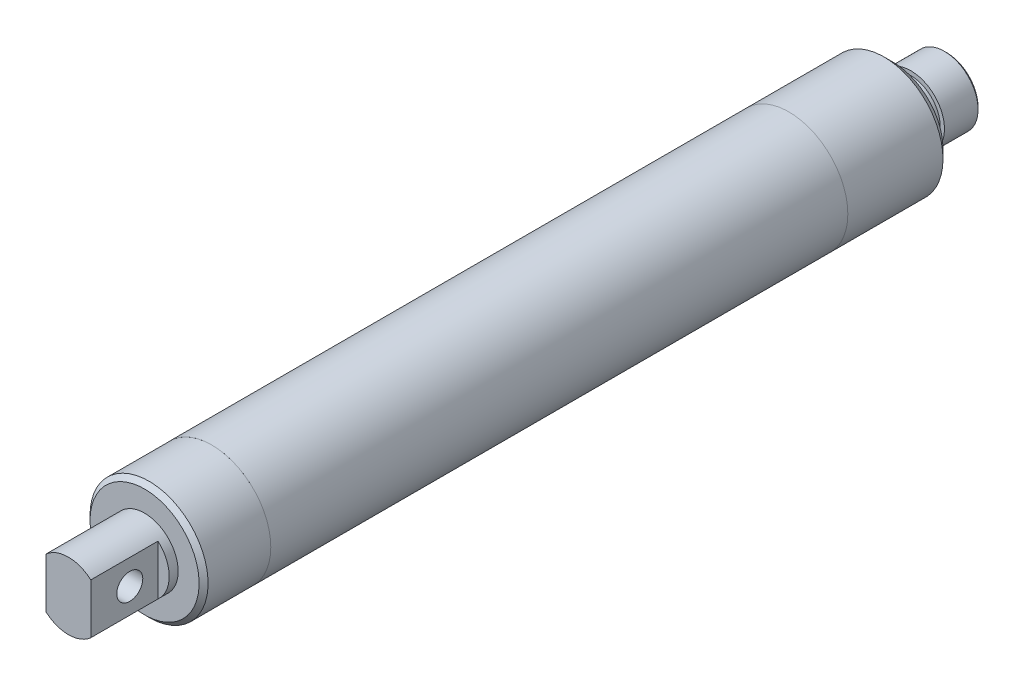
SolidWorks part; units mm, degrees
note: '?' marks a value the reader was unsure of.
ref_plane "Front" through (0, 0, 0) normal (0, 0, 1) x (1, 0, 0)
ref_plane "Top" through (0, 0, 0) normal (0, 1, 0) x (1, 0, 0)
ref_plane "Right" through (0, 0, 0) normal (1, 0, 0) x (0, 0, -1)
sketch "Sketch1" plane through (0, 0, 0) normal (0, 0, 1) x (1, 0, 0)
  circle A0 centre (0, 0) radius 16.7322
  circle A1 centre (0, 0) radius 15.4039
  dimension "D1" = 33.4645
extrude "Cyclendar" add sketch "Sketch1" along normal blind 163.576
ref_plane "Plane1" through (0, 0, 81.788) normal (0, 0, 1) x (1, 0, 0)
sketch "Sketch2" plane through (0, 0, 0) normal (0, 0, 1) x (1, 0, 0)
  circle A0 centre (0, 0) radius 16.7322
  circle A1 centre (0, 0) radius 5.588
  dimension "D1" = 11.176
extrude "Nose" add sketch "Sketch2" against normal blind 29.5148 separate body
chamfer "Nose_Chamfer" distance 2.54 angle 45 1 edges at (16.7322, 0, -29.5148)
sketch "Sketch3" plane through (0, 0, 0) normal (1, 0, 0) x (0, 0, -1)
  line L0 (0, 0) -> (11.049, 0) construction
  circle A0 centre (11.049, 0) radius 5.08
  dimension "D2" = 10.16
  dimension "D1" = 11.049
extrude "Cut-Extrude1" cut sketch "Sketch3" against normal up to next
sketch "Sketch4" plane through (0, 0, 0) normal (0, 1, 0) x (1, 0, 0)
  line L1 (-8.89, 44.7548) -> (-9.525, 44.1198)
  line L3 (-5.588, 44.7548) -> (-8.89, 44.7548)
  line L4 (-9.525, 44.1198) -> (-9.525, 34.5948)
  line L6 (-8.3185, 34.5948) -> (-8.3185, 31.4198)
  line L7 (-8.3185, 31.4198) -> (-9.525, 31.4198)
  line L8 (-9.525, 31.4198) -> (-9.525, 29.5148)
  line L9 (-9.525, 29.5148) -> (-5.588, 29.5148)
  line L10 (-9.525, 34.5948) -> (-8.3185, 34.5948)
  line L11 (-5.588, 29.5148) -> (-5.588, 44.7548)
  point P6 (-9.525, 44.7548)
ref_axis "Axis1" through (0, 0, -26.9748) along (0, 0, 1)?
revolve "Revolve1" add sketch "Sketch4" angle 360 about axis through (0, 0, -26.9748) along (0, 0, 1)
sketch "Sketch6" plane through (0, 0, 163.576) normal (0, 0, 1) x (1, 0, 0)
  circle A0 centre (0, 0) radius 16.7322 construction
  circle A1 centre (0, 0) radius 16.7322
extrude "Tail" add sketch "Sketch6" along normal blind 19.05 separate body
chamfer "Tail_Chamfer" distance 1.27 angle 45 1 edges at (16.7322, 0, 182.626)
sketch "Sketch7" plane through (0, 0, 182.626) normal (0, 0, 1) x (1, 0, 0)
  circle A0 centre (0, 0) radius 9.525
  dimension "D1" = 19.05
extrude "Tail_Mount" add sketch "Sketch7" along normal blind 2.54
sketch "Sketch8" plane through (0, 0, 185.166) normal (0, 0, 1) x (1, 0, 0)
  circle A0 centre (0, 0) radius 9.525 construction
  circle A1 centre (0, 0) radius 9.525
extrude "Boss-Extrude5" add sketch "Sketch8" along normal blind 19.05
sketch "Sketch9" plane through (0, 0, 0) normal (1, 0, 0) x (0, 0, -1)
  line L0 (-163.576, 16.7322) -> (-163.576, -16.7322) construction
  line L1 (-163.576, 16.7322) -> (-163.576, -16.7322) construction
  line L2 (-163.576, 0) -> (-174.752, 0) construction
  circle A0 centre (-174.752, 0) radius 5.08
  dimension "D2" = 10.16
  dimension "D1" = 11.176
extrude "Cut-Extrude2" cut sketch "Sketch9" against normal up to next
sketch "Sketch10" plane through (0, 0, 204.216) normal (0, 0, 1) x (1, 0, 0)
  line L0 (0, -9.525) -> (0, 9.525) construction
  line L1 (6.35, -9.525) -> (6.35, 9.525)
  line L2 (-6.35, -9.525) -> (-6.35, 9.525)
  line L3 (-6.35, -9.525) -> (-12.7995, -9.525)
  line L4 (-12.7995, -9.525) -> (-12.7995, 9.525)
  line L5 (-12.7995, 9.525) -> (-6.35, 9.525)
  line L6 (6.35, -9.525) -> (14.8147, -9.525)
  line L7 (14.8147, -9.525) -> (14.8147, 9.525)
  line L8 (14.8147, 9.525) -> (6.35, 9.525)
  circle A2 centre (0, 0) radius 9.525 construction
extrude "Cut-Extrude3" cut sketch "Sketch10" against normal blind 19.05
sketch "Sketch11" plane through (-6.35, 0, 0) normal (-1, 0, 0) x (0, 0, 1)
  line L0 (204.216, 0) -> (196.85, 0) construction
  line L1 (204.216, -7.0995) -> (204.216, 7.0995) construction
  circle A0 centre (193.167, 0) radius 3.683
  dimension "D2" = 7.366
  dimension "D1" = 7.366
extrude "Cut-Extrude4" cut sketch "Sketch11" against normal up to next (12.7 mm away)
sketch "Sketch12" plane through (0, 0, 163.576) normal (0, 0, -1) x (-1, 0, 0)
  circle A0 centre (0, 0) radius 7.62
  dimension "D1" = 15.24
extrude "Cut-Extrude5" cut sketch "Sketch12" against normal blind 13.97
